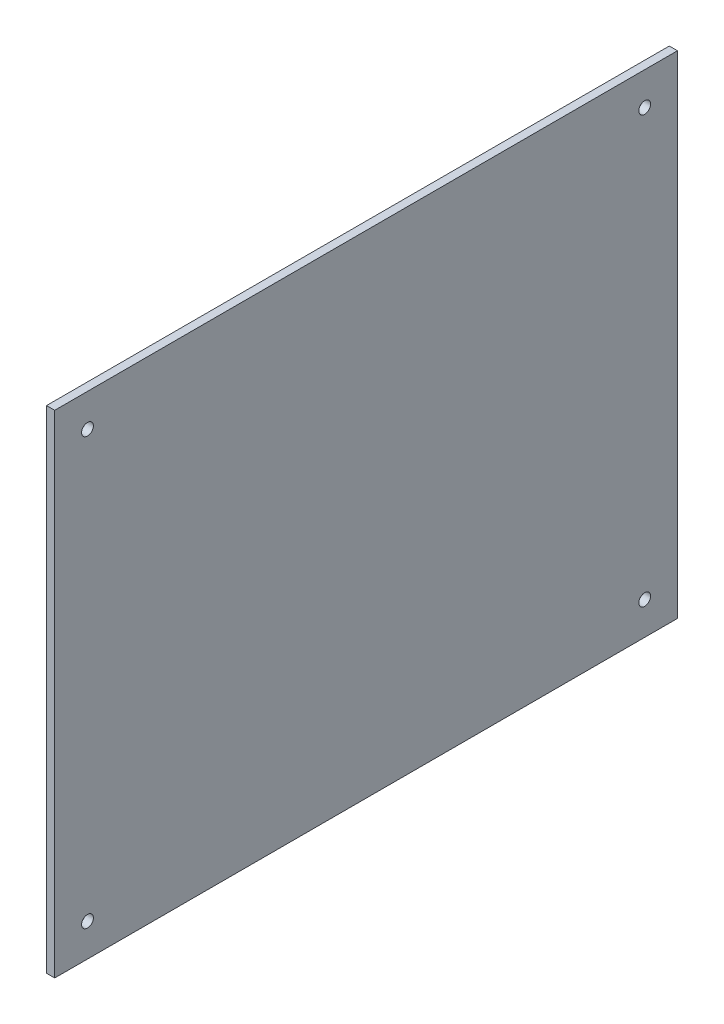
SolidWorks part; units mm, degrees
ref_plane "Front Plane" through (0, 0, 0) normal (0, 0, 1) x (1, 0, 0)
ref_plane "Top Plane" through (0, 0, 0) normal (0, 1, 0) x (1, 0, 0)
ref_plane "Right Plane" through (0, 0, 0) normal (1, 0, 0) x (0, 0, -1)
sketch "Sketch1" plane through (0, 0, 0) normal (1, 0, 0) x (0, 0, -1)
  line L1 (0, 0) -> (241.3, 0)
  line L2 (0, 0) -> (0, 190.5)
  line L3 (0, 190.5) -> (241.3, 190.5)
  line L4 (241.3, 0) -> (241.3, 190.5)
  dimension "D1" = 241.3
  dimension "D2" = 190.5
extrude "Boss-Extrude1" add sketch "Sketch1" along normal blind 3.175
sketch "Sketch2" plane through (3.175, 0, 0) normal (1, 0, 0) x (0, 0, -1)
  line L2 (-1000, 95.25) -> (49000, 95.25) construction
  line L3 (0, 190.5) -> (0, 0) construction
  line L4 (120.65, -809.5) -> (120.65, 49190.5) construction
  line L5 (241.3, 190.5) -> (0, 190.5) construction
  line L6 (1228.6, 95.25) -> (-48771.4, 95.25) construction
  line L7 (241.3, 0) -> (241.3, 190.5) construction
  line L8 (0, 0) -> (241.3, 0) construction
  circle A8 centre (228.6, 12.7) radius 2.286
  circle A9 centre (228.6, 177.8) radius 2.286
  circle A10 centre (12.7, 12.7) radius 2.286
  circle A11 centre (12.7, 177.8) radius 2.286
  point P15 (0, 95.25)
  point P20 (120.65, 190.5)
  dimension "D1" = 4.572
  dimension "D2" = 12.7
  dimension "D3" = 12.7
extrude "Cut-Extrude1" cut sketch "Sketch2" against normal through all
